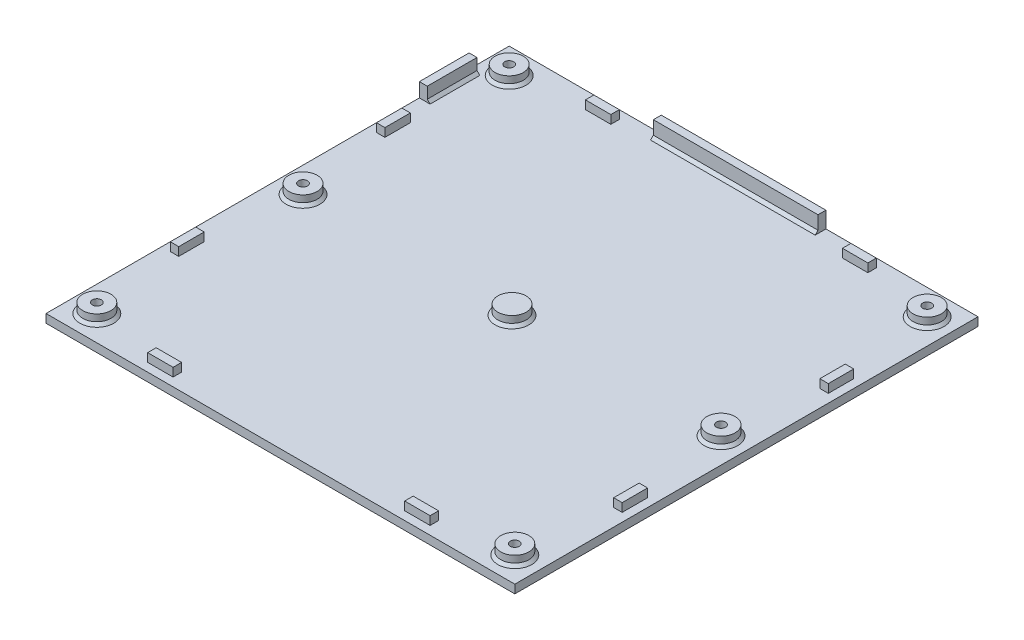
SolidWorks part; units mm, degrees
ref_plane "前视基准面" through (0, 0, 0) normal (0, 0, 1) x (1, 0, 0)
ref_plane "上视基准面" through (0, 0, 0) normal (0, 1, 0) x (1, 0, 0)
ref_plane "右视基准面" through (0, 0, 0) normal (1, 0, 0) x (0, 0, -1)
sketch "草图1" plane through (0, 0, 0) normal (0, 1, 0) x (1, 0, 0)
  line L1 (-83, 82) -> (83, 82)
  line L2 (-83, 82) -> (-83, -82)
  line L3 (-83, -82) -> (83, -82)
  line L4 (83, 82) -> (83, -82)
  line L5 (-83, 82) -> (83, -82) construction
  line L6 (-83, -82) -> (83, 82) construction
  point P0 (0, 0)
  dimension "D1" = 166
  dimension "D2" = 164
extrude "凸台-拉伸1" add sketch "草图1" along normal blind 3
sketch "草图2" plane through (0, 0, 0) normal (0, 1, 0) x (1, 0, 0)
  line L0 (-83, 82) -> (-83, -82) construction
  line L1 (-74, 73) -> (74, 73) construction
  line L2 (-74, 73) -> (-74, -73) construction
  line L3 (-74, -73) -> (74, -73) construction
  line L4 (74, 73) -> (74, -73) construction
  line L5 (83, 82) -> (-83, 82) construction
  line L6 (83, -82) -> (83, 82) construction
  line L7 (-83, -82) -> (83, -82) construction
  circle A0 centre (-74, 73) radius 1.6
  circle A1 centre (-74, 0) radius 1.6
  circle A2 centre (74, 0) radius 1.6
  circle A3 centre (74, 73) radius 1.6
  circle A4 centre (74, -73) radius 1.6
  circle A5 centre (-74, -73) radius 1.6
  dimension "D5" = 3.2
  dimension "D1" = 9
  dimension "D2" = 9
  dimension "D3" = 9
  dimension "D4" = 9
extrude "切除-拉伸1" cut sketch "草图2" along normal up to next
chamfer "倒角1" distance 2 angle 45 6 edges at (74, 0, -71.4) (74, 0, 74.6) (74, 0, 1.6) (-74, 0, -71.4) (-74, 0, 1.6) (-74, 0, 74.6)
sketch "草图3" plane through (0, 0, 0) normal (0, 1, 0) x (1, 0, 0)
  line L0 (83, 82) -> (-83, 82) construction
  line L1 (29.15, 82) -> (-29.15, 82)
  line L2 (29.15, 82) -> (29.15, 79.2)
  line L3 (29.15, 79.2) -> (-29.15, 79.2)
  line L4 (-29.15, 82) -> (-29.15, 79.2)
  line L5 (0, 82) -> (0, 79.2) construction
  point P9 (0, 82)
  point P11 (0, 79.2)
  dimension "D1" = 2.8
  dimension "D2" = 58.3
  dimension "D3" = 0
extrude "凸台-拉伸2" add sketch "草图3" along normal blind 5.75 from surface starting at face at (74, 3, 74.6)
sketch "草图4" plane through (0, 0, 0) normal (0, 1, 0) x (1, 0, 0)
  line L0 (-83, 82) -> (-83, -82) construction
  line L1 (-83, 67.8) -> (-80.2, 67.8)
  line L2 (-83, 67.8) -> (-83, 50.2)
  line L3 (-83, 50.2) -> (-80.2, 50.2)
  line L4 (-80.2, 67.8) -> (-80.2, 50.2)
  line L5 (-29.15, 82) -> (-83, 82) construction
  point P8 (-80.2, 59)
  dimension "D1" = 23
  dimension "D2" = 17.6
  dimension "D3" = 2.8
extrude "凸台-拉伸3" add sketch "草图4" along normal blind 5 from surface starting at face at (74, 3, 74.6)
sketch "草图5" plane through (0, 0, 0) normal (0, 1, 0) x (1, 0, 0)
  circle A0 centre (-74, 73) radius 5
  circle A1 centre (-74, 0) radius 5
  circle A2 centre (-74, -73) radius 5
  circle A3 centre (74, -73) radius 5
  circle A4 centre (74, 0) radius 5
  circle A5 centre (74, 73) radius 5
  circle A6 centre (0, 0) radius 5
  circle A7 centre (74, -73) radius 1.6
  circle A8 centre (74, -73) radius 1.6
  circle A9 centre (-74, -73) radius 1.6
  circle A10 centre (-74, -73) radius 1.6
  circle A11 centre (-74, 0) radius 1.6
  circle A12 centre (-74, 0) radius 1.6
  circle A13 centre (74, 0) radius 1.6
  circle A14 centre (74, 0) radius 1.6
  circle A15 centre (74, 73) radius 1.6
  circle A16 centre (74, 73) radius 1.6
  circle A17 centre (-74, 73) radius 1.6
  circle A18 centre (-74, 73) radius 1.6
  dimension "D1" = 10
  dimension "D2" = 0
  dimension "D3" = 0
  dimension "D4" = 0
  dimension "D5" = 0
  dimension "D6" = 0
  dimension "D7" = 0
extrude "凸台-拉伸4" add sketch "草图5" along normal blind 3.4 from surface starting at face at (-27.2, 3, -46.5333)
chamfer "倒角2" distance 1 angle 45 9 edges at (74, 3, 78) (-74, 3, 78) (-74, 3, 5) (74, 3, 5) (74, 3, -68) (-80.2, 3, -59) (0, 3, -79.2) (-74, 3, -68) (0, 3, 5)
sketch "草图6" plane through (0, 0, 0) normal (0, 1, 0) x (1, 0, 0)
  line L0 (-80, 79) -> (-83, 79) construction
  line L1 (-80, 79) -> (80, 79) construction
  line L2 (-80, 79) -> (-80, -79) construction
  line L3 (-80, -79) -> (80, -79) construction
  line L4 (80, 79) -> (80, -79) construction
  line L6 (-80, 79) -> (-80, 82) construction
  line L7 (-29.15, 82) -> (-83, 82) construction
  line L8 (80, -79) -> (83, -79) construction
  line L9 (83, -82) -> (83, 82) construction
  line L10 (80, -79) -> (80, -82) construction
  line L11 (-83, -82) -> (83, -82) construction
  line L12 (-83, 50.2) -> (-83, -82) construction
  line L13 (-74, 73) -> (-74, 0) construction
  line L14 (-41, 79) -> (-50, 79)
  line L15 (-41, 79) -> (-41, 76)
  line L16 (-41, 76) -> (-50, 76)
  line L17 (-50, 79) -> (-50, 76)
  line L18 (50, 79) -> (41, 79)
  line L19 (50, 79) -> (50, 76)
  line L20 (50, 76) -> (41, 76)
  line L21 (41, 79) -> (41, 76)
  line L22 (-80, 41) -> (-77, 41)
  line L23 (-80, 41) -> (-80, 32)
  line L24 (-80, 32) -> (-77, 32)
  line L25 (-77, 41) -> (-77, 32)
  line L26 (80, 41) -> (77, 41)
  line L27 (80, 41) -> (80, 32)
  line L28 (80, 32) -> (77, 32)
  line L29 (77, 41) -> (77, 32)
  line L30 (-80, -32) -> (-77, -32)
  line L31 (-80, -32) -> (-80, -41)
  line L32 (-80, -41) -> (-77, -41)
  line L33 (-77, -32) -> (-77, -41)
  line L34 (80, -32) -> (77, -32)
  line L35 (80, -32) -> (80, -41)
  line L36 (80, -41) -> (77, -41)
  line L37 (77, -32) -> (77, -41)
  line L38 (-50, -76) -> (-41, -76)
  line L39 (-50, -76) -> (-50, -79)
  line L40 (-50, -79) -> (-41, -79)
  line L41 (-41, -76) -> (-41, -79)
  line L42 (-74, 0) -> (-74, -73) construction
  line L44 (41, -79) -> (50, -79)
  line L45 (41, -79) -> (41, -76)
  line L46 (41, -76) -> (50, -76)
  line L47 (50, -79) -> (50, -76)
  point P52 (-74, -36.5)
  point P53 (-77, -36.5)
  point P54 (-74, 36.5)
  point P55 (-77, 36.5)
  dimension "D1" = 3
  dimension "D2" = 30
  dimension "D3" = 30
  dimension "D4" = 9
  dimension "D5" = 3
extrude "凸台-拉伸5" add sketch "草图6" along normal blind 3 from surface starting at face at (0, 3, 6)
